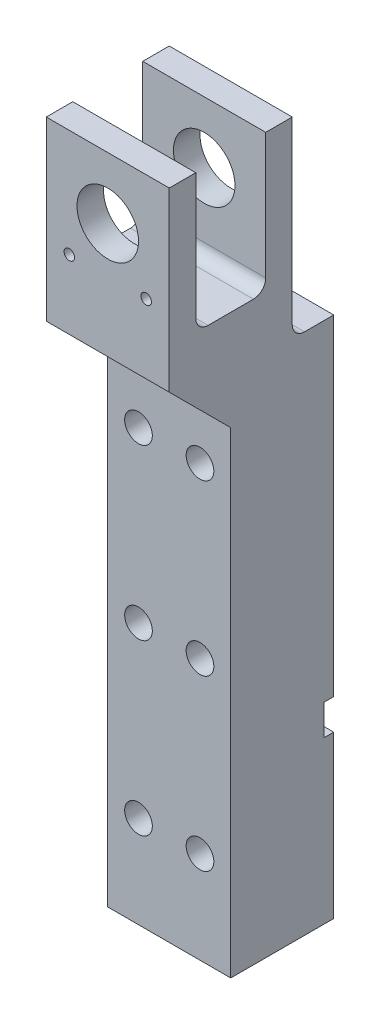
SolidWorks part; units mm, degrees
ref_plane "前视基准面" through (0, 0, 0) normal (0, 0, 1) x (1, 0, 0)
ref_plane "上视基准面" through (0, 0, 0) normal (0, 1, 0) x (1, 0, 0)
ref_plane "右视基准面" through (0, 0, 0) normal (1, 0, 0) x (0, 0, -1)
sketch "草图1" plane through (0, 0, 0) normal (0, 0, 1) x (1, 0, 0)
  line L1 (40, -232.5) -> (-40, -232.5)
  line L2 (40, -232.5) -> (40, 232.5)
  line L3 (40, 232.5) -> (-40, 232.5)
  line L4 (-40, -232.5) -> (-40, 232.5)
  line L5 (40, -232.5) -> (-40, 232.5) construction
  line L6 (40, 232.5) -> (-40, -232.5) construction
  point P0 (0, 0)
  dimension "D1" = 80
  dimension "D2" = 465
extrude "凸台-拉伸1" add sketch "草图1" along normal blind 107
sketch "草图2" plane through (-40, 0, 0) normal (-1, 0, 0) x (0, 0, 1)
  line L0 (27, 232.5) -> (27, 115.5)
  line L1 (107, 232.5) -> (0, 232.5) construction
  line L2 (19, 107.5) -> (0, 107.5)
  line L3 (0, 232.5) -> (0, -232.5) construction
  line L4 (0, 107.5) -> (0, 232.5)
  line L5 (0, 232.5) -> (27, 232.5)
  line L6 (107, 232.5) -> (107, -232.5) construction
  line L7 (44.25, 232.5) -> (44.25, 142.5)
  line L8 (44.25, 142.5) -> (89.75, 142.5)
  line L9 (89.75, 142.5) -> (89.75, 232.5)
  line L10 (89.75, 232.5) -> (44.25, 232.5)
  line L11 (27, 232.5) -> (107, 232.5) construction
  line L12 (67, 232.5) -> (67, 78.872) construction
  arc A0 (27, 115.5) -> (19, 107.5) centre (19, 115.5) cw
  dimension "D3" = 8
  dimension "D1" = 125
  dimension "D2" = 80
  dimension "D4" = 45.5
  dimension "D5" = 90
extrude "切除-拉伸1" cut sketch "草图2" against normal up to next
sketch "草图3" plane through (-40, 0, 0) normal (-1, 0, 0) x (0, 0, 1)
  line L0 (107, 117.5) -> (67, 77.5)
  line L1 (107, 232.5) -> (107, -232.5) construction
  line L2 (67, 77.5) -> (67, -232.5)
  line L3 (107, -232.5) -> (0, -232.5) construction
  line L4 (67, -232.5) -> (107, -232.5)
  line L5 (107, -232.5) -> (107, 117.5)
  line L6 (0, 107.5) -> (0, -232.5) construction
  line L7 (107, 232.5) -> (89.75, 232.5) construction
  dimension "D1" = 40
  dimension "D2" = 67
  dimension "D3" = 115
extrude "切除-拉伸2" cut sketch "草图3" against normal up to next
sketch "草图4" plane through (0, 0, 107) normal (0, 0, 1) x (1, 0, 0)
  line L0 (0, 232.5) -> (0, 117.5) construction
  line L1 (40, 232.5) -> (-40, 232.5) construction
  line L2 (40, 117.5) -> (-40, 117.5) construction
  circle A0 centre (0, 192.5) radius 20
  dimension "D1" = 40
  dimension "D2" = 40
extrude "切除-拉伸3" cut sketch "草图4" against normal up to surface (80 mm away) up to face at (0, 174, 27)
hole_wizard "M8 螺纹孔1" positions "草图6" profile "草图7" tap size "M8" standard "GB" end condition up to next
sketch "草图6" plane through (0, 0, 107) normal (0, 0, 1) x (1, 0, 0)
  line L0 (0, 192.5) -> (0, 153.2321) construction
  point P0 (-25, 162.5)
  point P2 (25, 162.5)
  dimension "D1" = 50
  dimension "D2" = 30
sketch "草图7" plane through (-25, 162.5, 107) normal (1, 0, 0) x (0, -1, 0)
  line L0 (0, 0) -> (0, 17.25)
  line L1 (0, 17.25) -> (3.4, 17.25)
  line L2 (3.4, 17.25) -> (3.4, 0)
  line L5 (3.4, 0) -> (0, 0)
  line L11 (0, -6.35) -> (0, 107.95) construction
  dimension "通孔螺纹孔钻头直径" = 6.8
  dimension "通孔螺纹孔钻头深度" = 17.25
cosmetic thread "孔螺蚊线1" parameters "D2"=8
cosmetic thread "孔螺蚊线2" parameters "D2"=8
sketch "草图8" plane through (0, 0, 0) normal (0, 0, -1) x (-1, 0, 0)
  line L0 (0, 0) -> (0, 93.2983) construction
  line L1 (0, 192.5) -> (-90.5087, 192.5) construction
  circle A0 centre (-20, 47.5) radius 9
  dimension "D1" = 18
  dimension "D3" = 145
  dimension "D2" = 40
extrude "切除-拉伸4" cut sketch "草图8" against normal up to next
pattern_linear "阵列(线性)1" count 2 spacing 40 along (-1, 0, 0) count 3 spacing 110 along (0, -1, 0) of "切除-拉伸4"
sketch "草图9" plane through (0, 0, 0) normal (0, 0, -1) x (-1, 0, 0)
  line L0 (-40, -107.5) -> (40, -107.5)
  line L1 (-40, -232.5) -> (-40, 107.5) construction
  line L2 (40, 107.5) -> (40, -232.5) construction
  line L3 (40, -107.5) -> (40, -127.5)
  line L4 (40, -127.5) -> (-40, -127.5)
  line L5 (-40, -127.5) -> (-40, -107.5)
  line L6 (-40, -117.5) -> (40, -117.5) construction
  circle A0 centre (-20, -62.5) radius 9 construction
  dimension "D1" = 20
  dimension "D2" = 55
extrude "切除-拉伸5" cut sketch "草图9" against normal blind 6.5
hole_wizard "M8 螺纹孔2" positions "草图11" profile "草图12" tap size "M8" standard "GB"
sketch "草图11" plane through (0, 0, 6.5) normal (0, 0, -1) x (-1, 0, 0)
  line L0 (0, -127.5) -> (0, -107.5) construction
  line L1 (-40, -127.5) -> (40, -127.5) construction
  line L2 (40, -107.5) -> (-40, -107.5) construction
  point P0 (-20, -117.5)
  point P2 (20, -117.5)
  point P17 (0, -117.5)
  dimension "D1" = 40
sketch "草图12" plane through (20, -117.5, 6.5) normal (1, 0, 0) x (0, 1, 0)
  line L0 (0, 0) -> (0, 27.0429)
  line L1 (0, 27.0429) -> (3.4, 25)
  line L2 (3.4, 25) -> (3.4, 0)
  line L5 (3.4, 0) -> (0, 0)
  line L10 (0, 27.0429) -> (-3.4, 25) construction
  line L11 (0, -6.35) -> (0, 107.95) construction
  dimension "螺纹孔钻头直径" = 6.8
  dimension "螺纹孔钻头深度" = 25
  dimension "导头角度" = 118
cosmetic thread "孔螺蚊线3" parameters "D1"=25, "D2"=8
cosmetic thread "孔螺蚊线4" parameters "D1"=25, "D2"=8
fillet "圆角1" radius 8 2 edges at (0, 142.5, 89.75) (0, 142.5, 44.25)
